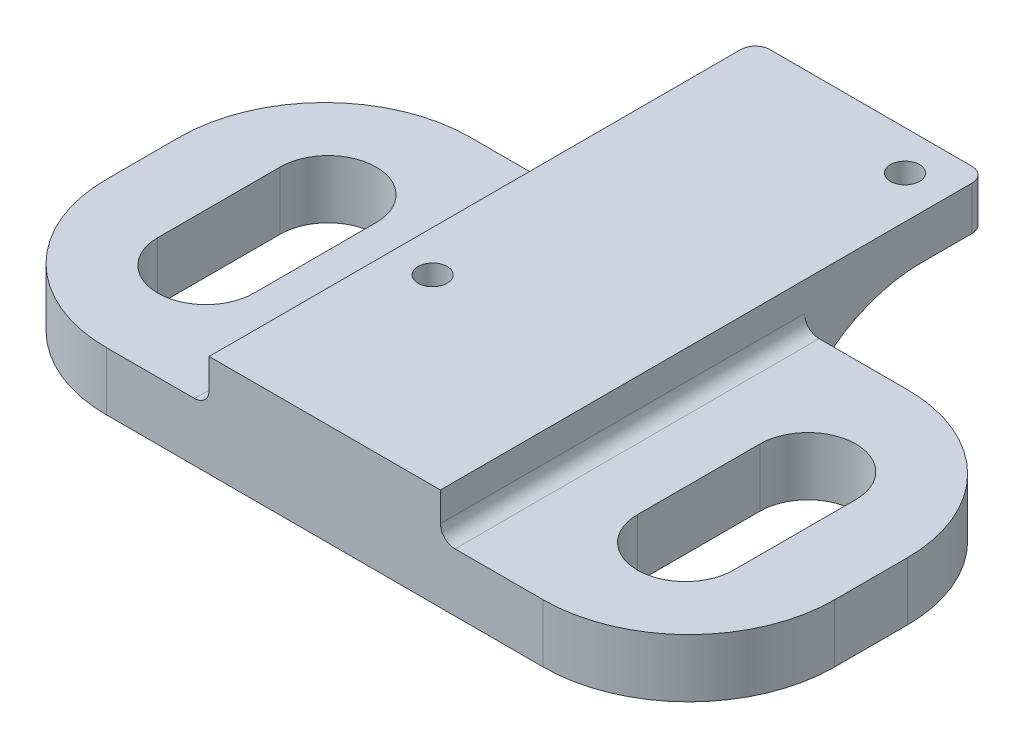
SolidWorks part; units mm, degrees
ref_plane "Front Plane" through (0, 0, 0) normal (0, 0, 1) x (1, 0, 0)
ref_plane "Top Plane" through (0, 0, 0) normal (0, 1, 0) x (1, 0, 0)
ref_plane "Right Plane" through (0, 0, 0) normal (1, 0, 0) x (0, 0, -1)
sketch "Sketch1" plane through (0, 0, 0) normal (0, 1, 0) x (1, 0, 0)
  line L1 (0, 0) -> (50, 0)
  line L2 (0, 0) -> (0, 25)
  line L3 (0, 25) -> (50, 25)
  line L4 (50, 0) -> (50, 25)
  dimension "D1" = 50
  dimension "D2" = 25
extrude "Boss-Extrude1" add sketch "Sketch1" along normal blind 4
sketch "Sketch2" plane through (0, 4, 0) normal (0, 1, 0) x (1, 0, 0)
  line L1 (17.06, 37.5) -> (32.94, 37.5)
  line L2 (17.06, 37.5) -> (17.06, 0)
  line L3 (17.06, 0) -> (32.94, 0)
  line L4 (32.94, 37.5) -> (32.94, 0)
  line L5 (0, 0) -> (50, 0) construction
  point P10 (25, 0)
  point P11 (25, 0)
  dimension "D1" = 15.88
  dimension "D2" = 37.5
extrude "Boss-Extrude2" add sketch "Sketch2" along normal blind 3
hole_wizard "M6 Clearance Slot1" positions "Sketch3" profile "Sketch4" size "M6" standard "ANSI Metric" slot yes end condition up to next
sketch "Sketch3" plane through (0, 4, 0) normal (0, 1, 0) x (1, 0, 0)
  line L0 (0, 25) -> (0, 0) construction
  line L1 (17.06, 25) -> (0, 25) construction
  line L2 (50, 25) -> (32.94, 25) construction
  line L3 (8.53, 5) -> (8.53, 20) construction
  point P0 (8.53, 12.5)
  point P2 (41.47, 12.5)
  point P9 (0, 12.5)
  point P13 (8.53, 25)
  point P17 (41.47, 25)
  dimension "D1" = 15
sketch "Sketch4" plane through (8.53, 4, -12.5) normal (1, 0, 0) x (0, 0, 1)
  line L0 (0, 0) -> (0, 4)
  line L1 (0, 4) -> (3.3, 4)
  line L2 (3.3, 4) -> (3.3, 0)
  line L5 (3.3, 0) -> (0, 0)
  line L11 (0, -6.35) -> (0, 107.95) construction
  dimension "Thru Hole Dia." = 6.6
  dimension "Thru Hole Depth" = 4
fillet "Fillet3" radius 10 4 edges at (50, 2, -25) (50, 2, 0) (0, 2, 0) (0, 2, -25)
fillet "Fillet4" radius 10 1 edges at (25, 4, -25)
fillet "Fillet5" radius 1 4 edges at (32.94, 4, -12.5) (17.06, 4, -12.5) (32.94, 5.5, -37.5) (17.06, 5.5, -37.5)
hole_wizard "Ø2.0mm Dowel Hole1" positions "Sketch5" profile "Sketch6" hole size "Ø2.0" standard "ANSI Metric" end condition up to next
sketch "Sketch5" plane through (0, 7, 0) normal (0, 1, 0) x (1, 0, 0)
  point P0 (30.04, 34.8)
  point P3 (19.88, 12.525)
sketch "Sketch6" plane through (30.04, 7, -34.8) normal (1, 0, 0) x (0, 0, 1)
  line L0 (0, 0) -> (0, 3)
  line L1 (0, 3) -> (1, 3)
  line L2 (1, 3) -> (1, 0)
  line L5 (1, 0) -> (0, 0)
  line L11 (0, -6.35) -> (0, 107.95) construction
  dimension "Thru Hole Dia." = 2
  dimension "Thru Hole Depth" = 3
